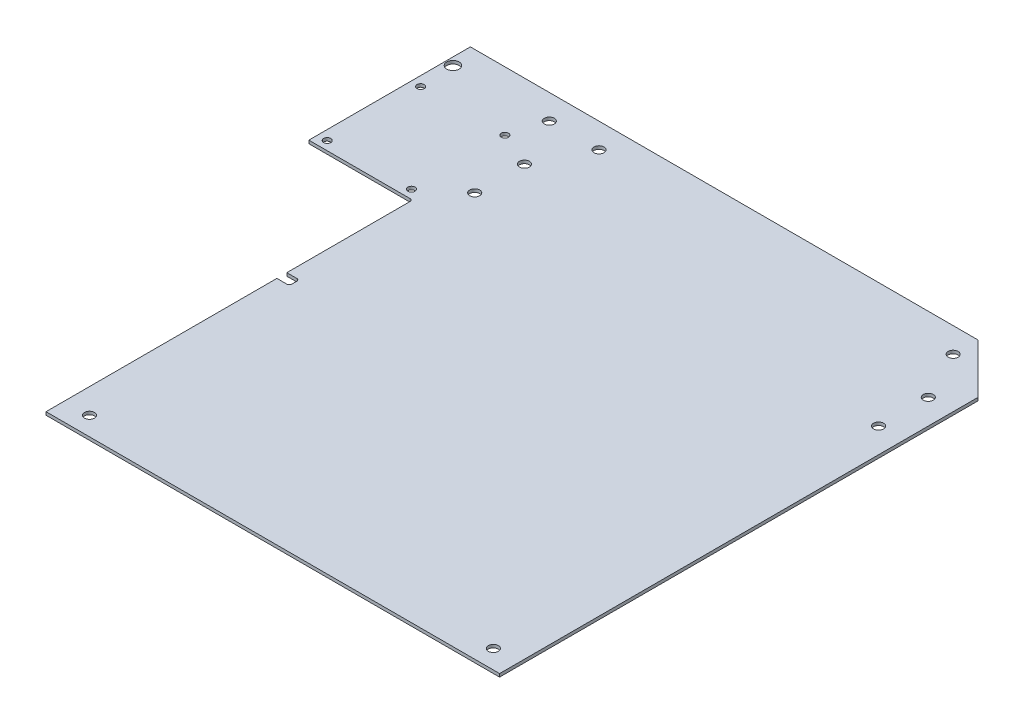
SolidWorks part; units mm, degrees
ref_plane "Front Plane" through (0, 0, 0) normal (0, 0, 1) x (1, 0, 0)
ref_plane "Top Plane" through (0, 0, 0) normal (0, 1, 0) x (1, 0, 0)
ref_plane "Right Plane" through (0, 0, 0) normal (1, 0, 0) x (0, 0, -1)
sketch "Sketch3" plane through (0, 0, 0) normal (0, 1, 0) x (1, 0, 0)
  line L1 (-177.119, 197.8912) -> (-149.179, 197.8912) construction
  line L2 (-96.1565, -3.6215) -> (-96.1565, 182.4335)
  line L3 (-177.119, 253.5535) -> (-177.119, 183.7035) construction
  line L5 (-149.179, 197.8912) -> (-149.179, 266.2535) construction
  line L6 (135.6185, -3.6215) -> (135.6185, 240.8535)
  line L7 (110.2185, 266.2535) -> (-70.7565, 266.2535)
  line L9 (-323.169, 266.2535) -> (337.231, 266.2535) construction
  line L11 (-70.7565, 266.2535) -> (-149.179, 266.2535)
  line L13 (135.6185, 240.8535) -> (110.2185, 266.2535)
  line L15 (-149.179, 266.2535) -> (-149.179, 183.7035)
  line L16 (-96.1565, -3.6215) -> (135.6185, -3.6215)
  line L17 (-149.179, 183.7035) -> (-97.4265, 183.7035)
  circle A0 centre (-83.4565, 202.7535) radius 6.35 construction
  arc A1 (-97.4265, 183.7035) -> (-96.1565, 182.4335) centre (-97.4265, 182.4335) cw
  dimension "D1" = 27.94
  dimension "D3" = 1.27
  dimension "D2" = 82.55
extrude "Boss-Extrude1" add sketch "Sketch3" along normal blind 1.5875
hole_wizard "#10 Clearance Hole1" positions "Sketch11" profile "Sketch12" hole size "#10" standard "ANSI Inch" end condition through all
sketch "Sketch11" plane through (0, 1.5875, 0) normal (0, 1, 0) x (1, 0, 0)
  point P0 (-83.4565, -25.8465)
  point P3 (-83.4565, 202.7535)
  point P6 (-83.4565, 228.1535)
  point P9 (-70.7565, 253.5535)
  point P12 (122.9185, 202.7535)
  point P15 (122.9185, 228.1535)
  point P18 (110.2185, 253.5535)
  point P21 (-83.4565, 5.9035)
  point P24 (122.9185, 5.9035)
  point P27 (-96.1565, 253.5535)
sketch "Sketch12" plane through (-83.4565, 1.5875, 25.8465) normal (1, 0, 0) x (0, 0, 1)
  line L0 (0, 0) -> (0, 1.5875)
  line L1 (0, 1.5875) -> (2.5527, 1.5875)
  line L2 (2.5527, 1.5875) -> (2.5527, 0)
  line L5 (2.5527, 0) -> (0, 0)
  line L11 (0, -6.35) -> (0, 107.95) construction
  dimension "Thru Hole Dia." = 5.1054
  dimension "Thru Hole Depth" = 1.5875
hole_wizard "1/4 (0.25) Diameter Hole1" positions "Sketch13" profile "Sketch14" hole size "1/4" standard "ANSI Inch" end condition through all
sketch "Sketch13" plane through (0, 0, 0) normal (0, -1, 0) x (-1, 0, 0)
  point P0 (145.369, 253.5535)
sketch "Sketch14" plane through (-145.369, 0, -253.5535) normal (1, 0, 0) x (0, 0, -1)
  line L0 (0, 0) -> (0, 1.5875)
  line L1 (0, 1.5875) -> (3.175, 1.5875)
  line L2 (3.175, 1.5875) -> (3.175, 0)
  line L5 (3.175, 0) -> (0, 0)
  line L11 (0, -6.35) -> (0, 107.95) construction
  dimension "Thru Hole Dia." = 6.35
  dimension "Thru Hole Depth" = 1.5875
hole_wizard "#6 Clearance Hole1" positions "Sketch15" profile "Sketch16" hole size "#6" standard "ANSI Inch" end condition through all
sketch "Sketch15" plane through (0, 1.5875, 0) normal (0, 1, 0) x (1, 0, 0)
  point P0 (-144.3052, 235.976)
  point P2 (-144.3052, 188.2264)
  point P4 (-101.2587, 188.2264)
  point P6 (-101.2587, 235.9784)
sketch "Sketch16" plane through (-144.3052, 1.5875, -235.976) normal (1, 0, 0) x (0, 0, 1)
  line L0 (0, 0) -> (0, 1.5875)
  line L1 (0, 1.5875) -> (1.8288, 1.5875)
  line L2 (1.8288, 1.5875) -> (1.8288, 0)
  line L5 (1.8288, 0) -> (0, 0)
  line L11 (0, -6.35) -> (0, 107.95) construction
  dimension "Thru Hole Dia." = 3.6576
  dimension "Thru Hole Depth" = 1.5875
sketch "Sketch17" plane through (0, 1.5875, 0) normal (0, 1, 0) x (1, 0, 0)
  line L0 (-96.1565, -3.6215) -> (-96.1565, 114.3615) construction
  line L1 (-96.1565, 182.4335) -> (-96.1565, -3.6215) construction
  line L2 (-96.1565, 114.3615) -> (-91.0765, 114.3615)
  line L3 (-89.8065, 115.6315) -> (-89.8065, 118.1715)
  line L4 (-91.0765, 119.4415) -> (-96.1565, 119.4415)
  line L5 (-96.1565, 119.4415) -> (-96.1565, 114.3615)
  arc A0 (-89.8065, 118.1715) -> (-91.0765, 119.4415) centre (-91.0765, 118.1715) ccw
  arc A1 (-91.0765, 114.3615) -> (-89.8065, 115.6315) centre (-91.0765, 115.6315) ccw
  point P10 (-89.8065, 119.4415)
  point P13 (-89.8065, 114.3615)
  dimension "D4" = 1.27
  dimension "D1" = 117.983
  dimension "D2" = 5.08
  dimension "D3" = 6.35
extrude "Cut-Extrude1" cut sketch "Sketch17" against normal through all
